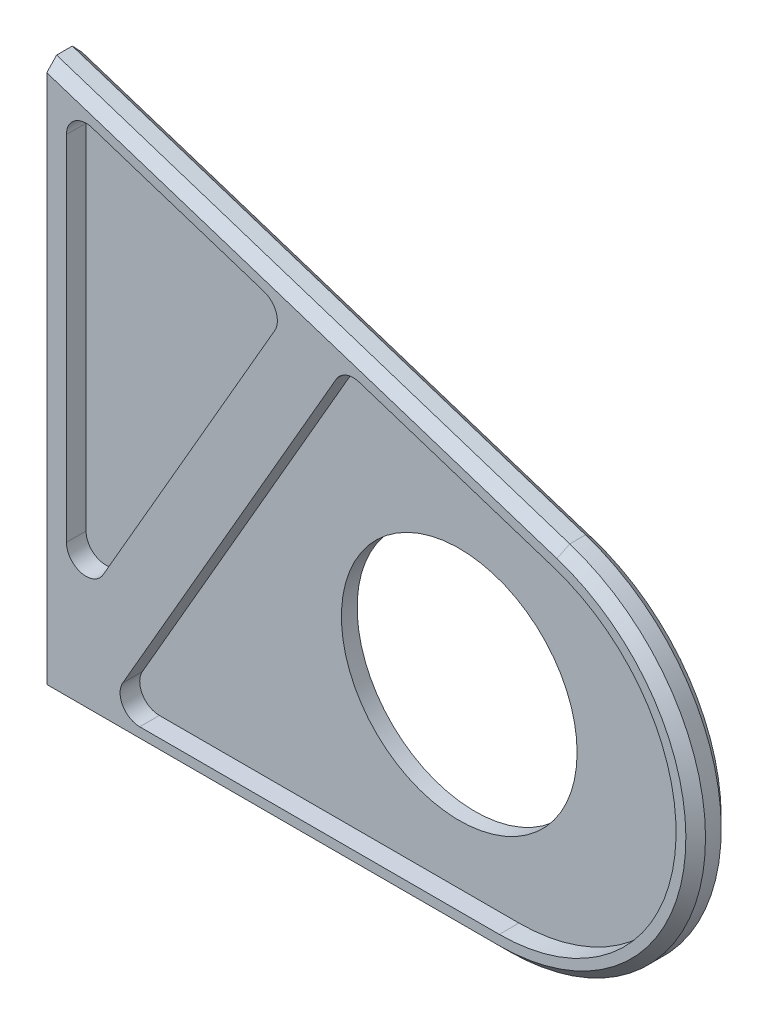
SolidWorks part; units mm, degrees
material "6061 合金"
ref_plane "前视基准面" through (0, 0, 0) normal (0, 0, 1) x (1, 0, 0)
ref_plane "上视基准面" through (0, 0, 0) normal (0, 1, 0) x (1, 0, 0)
ref_plane "右视基准面" through (0, 0, 0) normal (1, 0, 0) x (0, 0, -1)
other "Configuration Table"
sketch "草图1" plane through (0, 0, 0) normal (0, 0, 1) x (1, 0, 0)
  line L0 (0, 0) -> (0, 280)
  line L1 (0, 280) -> (861.7514, 0)
  line L3 (861.7514, 0) -> (0, 0)
  circle A0 centre (200, 100) radius 85 construction
  circle A1 centre (200, 100) radius 60
  dimension "D1" = 170
  dimension "D4" = 120
  dimension "D2" = 200
  dimension "D3" = 72
  dimension "D5" = 280
  dimension "D6" = 100
extrude "凸台-拉伸1" add sketch "草图1" along normal blind 8
fillet "圆角1" radius 100 1 edges at (861.7514, 0, 4)
sketch "草图2" plane through (0, 0, 8) normal (0, 0, 1) x (1, 0, 0)
  line L0 (10, 266.2362) -> (10, 35.359)
  line L1 (30, 10) -> (230.3762, 10)
  line L2 (10, 266.2362) -> (122.2414, 229.7667)
  line L3 (0, 0) -> (230.3762, 0)
  line L4 (261.2779, 195.1057) -> (0, 280)
  line L5 (0, 280) -> (0, 0)
  line L6 (0, 0) -> (230.3762, 0)
  line L7 (261.2779, 195.1057) -> (0, 280)
  line L8 (0, 280) -> (0, 0)
  line L9 (10, 35.359) -> (122.2414, 229.7667)
  line L10 (30, 10) -> (151.4105, 220.2891)
  line L11 (151.4105, 220.2891) -> (258.1878, 185.5951)
  line L12 (10, 35.359) -> (10, 10) construction
  line L13 (10, 10) -> (30, 10) construction
  arc A0 (230.3762, 10) -> (258.1878, 185.5951) centre (230.3762, 100) ccw
  arc A1 (230.3762, 0) -> (261.2779, 195.1057) centre (230.3762, 100) ccw
  arc A2 (230.3762, 0) -> (261.2779, 195.1057) centre (230.3762, 100) ccw
  dimension "D5" = 10
  dimension "D2" = 10
  dimension "D3" = 10
  dimension "D4" = 10
  dimension "D6" = 30
  dimension "D7" = 60
  dimension "D8" = 20
  dimension "D1" = 0
extrude "凸台-拉伸2" add sketch "草图2" along normal blind 10
fillet "圆角2" radius 10 5 edges at (10, 35.359, 13) (30, 10, 13) (122.2414, 229.7667, 13) (151.4105, 220.2891, 13) (10, 266.2362, 13)
chamfer "倒角1" distance 5 angle 45 6 edges at (130.639, 237.5528, 0) (115.1881, 0, 0) (329.1451, 84.3566, 0) (115.1881, 0, 18) (130.639, 237.5528, 18) (329.1451, 84.3566, 18)
